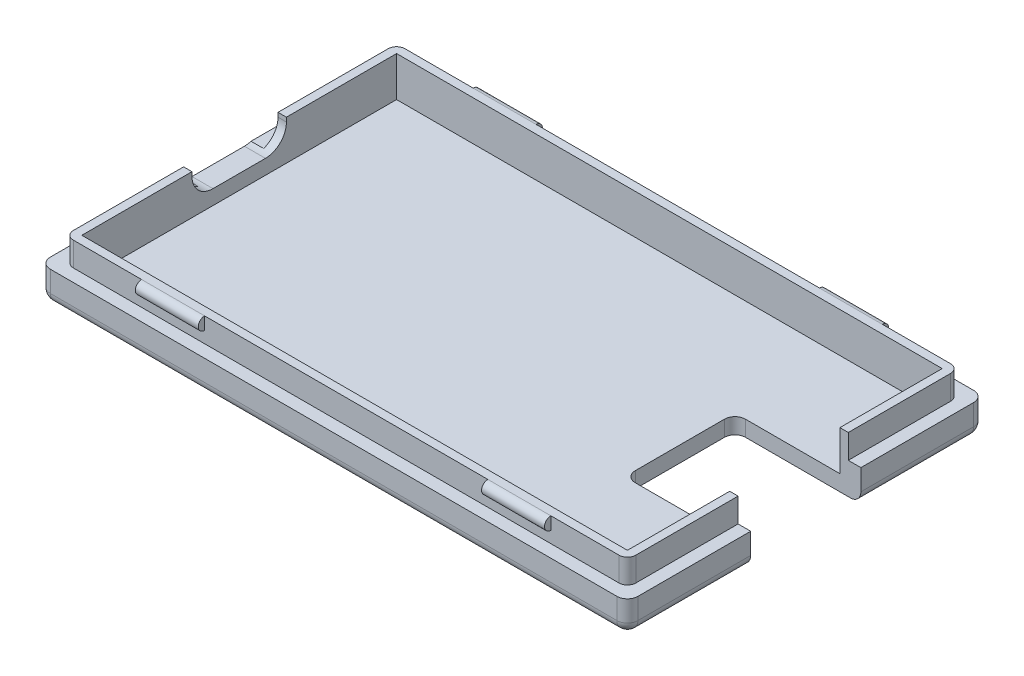
SolidWorks part; units mm, degrees
material "ABS"
ref_plane "Front Plane" through (0, 0, 0) normal (0, 0, 1) x (1, 0, 0)
ref_plane "Top Plane" through (0, 0, 0) normal (0, 1, 0) x (1, 0, 0)
ref_plane "Right Plane" through (0, 0, 0) normal (1, 0, 0) x (0, 0, -1)
sketch "Sketch1" plane through (0, 0, 0) normal (0, 1, 0) x (1, 0, 0)
  line L1 (28, -17) -> (-28, -17)
  line L2 (28, -17) -> (28, 17)
  line L3 (28, 17) -> (-28, 17)
  line L4 (-28, -17) -> (-28, 17)
  line L5 (28, -17) -> (-28, 17) construction
  line L6 (28, 17) -> (-28, -17) construction
  line L7 (26, -15) -> (-26, -15)
  line L8 (26, -15) -> (26, 15)
  line L9 (26, 15) -> (-26, 15)
  line L10 (-26, -15) -> (-26, 15)
  line L11 (26, -15) -> (-26, 15) construction
  line L12 (26, 15) -> (-26, -15) construction
  point P0 (0, 0)
  point P6 (0, 0)
  dimension "D1" = 56
  dimension "D2" = 34
  dimension "D3" = 2
  dimension "D4" = 2
extrude "Boss-Extrude1" add sketch "Sketch1" along normal blind 1.5 contours L10 L7 L8 L9 | L4 L1 L2 L3 L7 L10 L9 L8 region at (0, 0, 16.3449) region at (0, 0, 0)
extrude "Boss-Extrude2" add sketch "Sketch1<3>" along normal blind 3 contours L4 L1 L2 L3 L7 L10 L9 L8 region at (0, 0, 16.3449)
sketch "Sketch1<3>" plane through (0, 0, 0) normal (0, 1, 0) x (1, 0, 0) same geometry as "Sketch1"
sketch "Sketch2" plane through (0, 3, 0) normal (0, 1, 0) x (1, 0, 0)
  line L0 (26, 15) -> (26, -15) construction
  line L1 (-26, -15) -> (26, -15) construction
  line L2 (-26, -15) -> (-26, 15) construction
  line L3 (-26, 15) -> (26, 15) construction
  line L4 (26, 15) -> (26, -15)
  line L5 (-26, -15) -> (26, -15)
  line L6 (-26, -15) -> (-26, 15)
  line L7 (-26, 15) -> (26, 15)
  line L8 (-26.8, 15.8) -> (26.8, 15.8)
  line L9 (26.8, 15.8) -> (26.8, -15.8)
  line L10 (-26.8, -15.8) -> (26.8, -15.8)
  line L11 (-26.8, -15.8) -> (-26.8, 15.8)
  dimension "D1" = 0.8
extrude "Boss-Extrude3" add sketch "Sketch2" along normal blind 2.3
sketch "Sketch3" plane through (0, 3, 0) normal (0, 1, 0) x (1, 0, 0)
  line L0 (-28, -17) -> (-28, 17) construction
  line L1 (-28, -10.25) -> (-26.8, -10.25)
  line L2 (-28, -10.25) -> (-28, -6.5)
  line L3 (-28, -6.5) -> (-26.8, -6.5)
  line L4 (-26.8, -10.25) -> (-26.8, -6.5)
  line L5 (-26.8, 15.8) -> (-26.8, -15.8) construction
  line L6 (0, 0) -> (-10.9883, 0) construction
  line L7 (-28, 6.5) -> (-26.8, 6.5)
  line L8 (-26.8, 10.25) -> (-26.8, 6.5)
  line L9 (-28, 10.25) -> (-26.8, 10.25)
  line L10 (-28, 10.25) -> (-28, 6.5)
  dimension "D1" = 13
  dimension "D2" = 20.5
extrude "Cut-Extrude1" cut sketch "Sketch3" against normal blind 1
sketch "Sketch4" plane through (0, 0, 0) normal (1, 0, 0) x (0, 0, -1)
  line L0 (15.8, 5.3) -> (15.8, 3) construction
  line L1 (-15.8, 5.3) -> (-15.8, 3) construction
  circle A0 centre (15.8, 4.7) radius 0.6
  circle A1 centre (-15.8, 4.7) radius 0.6
  dimension "D1" = 1.2
extrude "Boss-Extrude4" add sketch "Sketch4" along normal blind 6 from offset 13.5
mirror "Mirror1" about plane through (0, 0, 0) normal (1, 0, 0) of "Boss-Extrude4"
fillet "Fillet1" radius 1 8 edges at (0, 0, 17) (28, 0, 0) (0, 0, -17) (-28, 0, 0) (28, 1.5, 17) (-28, 1.5, 17) (-28, 1.5, -17) (28, 1.5, -17)
fillet "Fillet2" radius 0.8 4 edges at (26.8, 4.15, 15.8) (-26.8, 4.15, 15.8) (-26.8, 4.15, -15.8) (26.8, 4.15, -15.8)
sketch "Sketch5" plane through (0, 0, 0) normal (1, 0, 0) x (0, 0, -1)
  line L0 (-15, 5.3) -> (15, 5.3) construction
  line L1 (-4.5, 9.6229) -> (4.5, 9.6229)
  line L2 (-4.5, 9.6229) -> (-4.5, 4.9)
  line L3 (-2.5, 2.9) -> (2.5, 2.9)
  line L4 (4.5, 9.6229) -> (4.5, 4.9)
  arc A0 (2.5, 2.9) -> (4.5, 4.9) centre (2.5, 4.9) ccw
  arc A1 (-4.5, 4.9) -> (-2.5, 2.9) centre (-2.5, 4.9) ccw
  point P4 (0, 9.6229)
  dimension "D2" = 2
  dimension "D1" = 9
  dimension "D3" = 2.4
extrude "Cut-Extrude2" cut sketch "Sketch5" against normal through all
sketch "Sketch7" plane through (0, 0, 0) normal (0, -1, 0) x (1, 0, 0)
  line L0 (28, 16) -> (28, -16) construction
  line L1 (32.0379, -5.25) -> (17, -5.25)
  line L2 (32.0379, -5.25) -> (32.0379, 5.25)
  line L3 (32.0379, 5.25) -> (17, 5.25)
  line L4 (16, -4.25) -> (16, 4.25)
  line L5 (32.0379, -5.25) -> (16, 5.25) construction
  line L6 (32.0379, 5.25) -> (16, -5.25) construction
  arc A0 (17, -5.25) -> (16, -4.25) centre (17, -4.25) cw
  arc A1 (16, 4.25) -> (17, 5.25) centre (17, 4.25) cw
  point P0 (24.019, 0)
  point P5 (0, 0)
  dimension "D2" = 1
  dimension "D1" = 10.5
  dimension "D3" = 11
extrude "Cut-Extrude4" cut sketch "Sketch7" against normal through all
